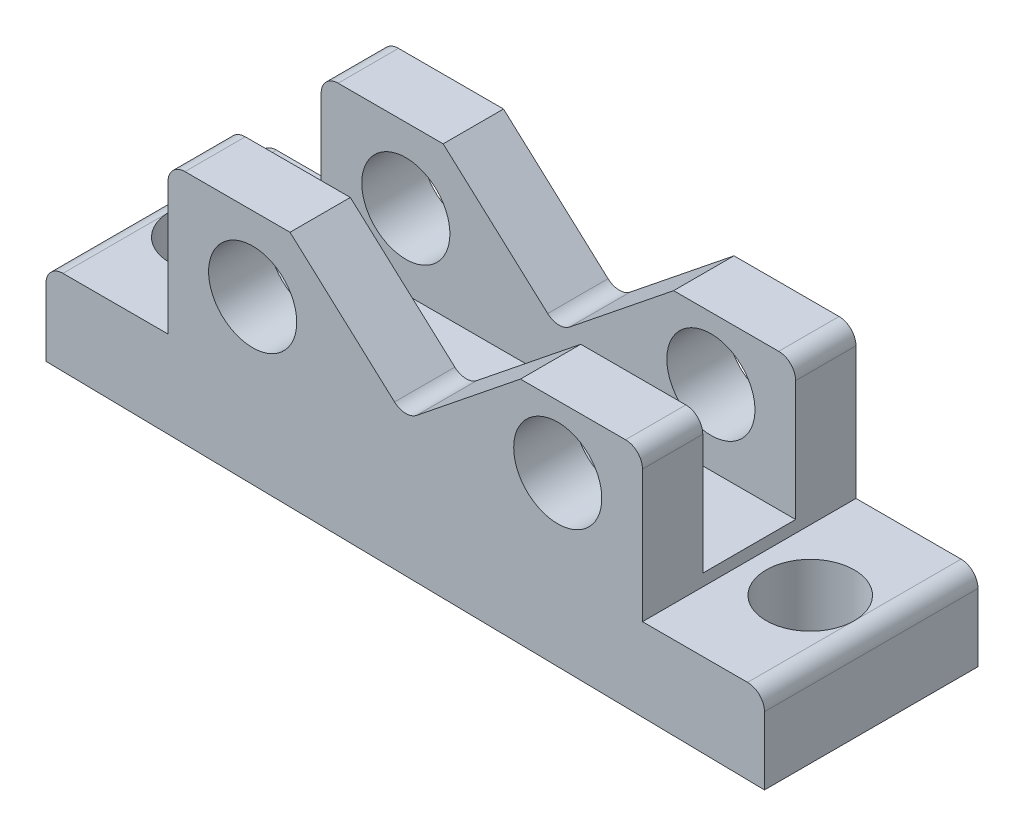
SolidWorks part; units mm, degrees
ref_plane "Front Plane" through (0, 0, 0) normal (0, 0, 1) x (1, 0, 0)
ref_plane "Top Plane" through (0, 0, 0) normal (0, 1, 0) x (1, 0, 0)
ref_plane "Right Plane" through (0, 0, 0) normal (1, 0, 0) x (0, 0, -1)
sketch "Sketch2" plane through (0, 0, 0) normal (0, 0, 1) x (1, 0, 0)
  line L0 (0, 0) -> (212, -3.5168)
  line L1 (212, -3.5168) -> (212, 21.4832)
  line L2 (212, 21.4832) -> (176, 21.4832)
  line L3 (176, 21.4832) -> (176, 65.4832)
  line L4 (176, 65.4832) -> (140, 65.4832)
  line L5 (0, 0) -> (0, 25)
  line L6 (0, 25) -> (36, 25)
  line L7 (36, 25) -> (36, 69)
  line L8 (36, 69) -> (72, 69)
  line L9 (72, 69) -> (106, 38.1932)
  line L10 (106, 38.1932) -> (140, 65.4832)
  dimension "D1" = 25
  dimension "D2" = 212
  dimension "D3" = 25
  dimension "D4" = 36
  dimension "D5" = 36
  dimension "D6" = 44
  dimension "D7" = 44
  dimension "D8" = 36
  dimension "D9" = 36
  dimension "D10" = 34
extrude "Boss-Extrude1" add sketch "Sketch2" along normal blind 63
sketch "Sketch10" plane through (0, 0, 0) normal (0, 0, -1) x (-1, 0, 0)
  circle A0 centre (-150.9983, 46.996) radius 13
extrude "Cut-Extrude3" cut sketch "Sketch10" against normal blind 70
sketch "Sketch12" plane through (0, 25, 0) normal (0, 1, 0) x (1, 0, 0)
  circle A0 centre (18, -31.5) radius 13
  circle A1 centre (194, -31.5) radius 13
extrude "Cut-Extrude4" cut sketch "Sketch12" against normal blind 70
sketch "Sketch16" plane through (0, 69, 0) normal (0, 1, 0) x (1, 0, 0)
  line L0 (72, -63) -> (72, 0) construction
  line L5 (176, -63) -> (176, 0) construction
  line L6 (36, -17.8074) -> (176, -17.8074)
  line L7 (36, -17.8074) -> (36, -45.2057)
  line L8 (36, -45.2057) -> (176, -45.2057)
  line L9 (176, -17.8074) -> (176, -45.2057)
extrude "Cut-Extrude6" cut sketch "Sketch16" against normal blind 44
sketch "Sketch17" plane through (0, 0, 63) normal (0, 0, 1) x (1, 0, 0)
  circle A0 centre (60.9744, 46.9788) radius 13
extrude "Cut-Extrude7" cut sketch "Sketch17" against normal blind 100
fillet "Fillet1" radius 5 1 edges at (106, 38.1932, 8.9037)
fillet "Fillet2" radius 5 1 edges at (106, 38.1932, 54.1029)
fillet "Fillet3" radius 5 1 edges at (212, 21.4832, 31.5)
fillet "Fillet4" radius 5 1 edges at (176, 65.4832, 54.1029)
fillet "Fillet5" radius 5 1 edges at (176, 65.4832, 8.9037)
fillet "Fillet6" radius 5 1 edges at (36, 69, 54.1029)
fillet "Fillet7" radius 5 1 edges at (36, 69, 8.9037)
fillet "Fillet8" radius 5 1 edges at (0, 25, 31.5)
